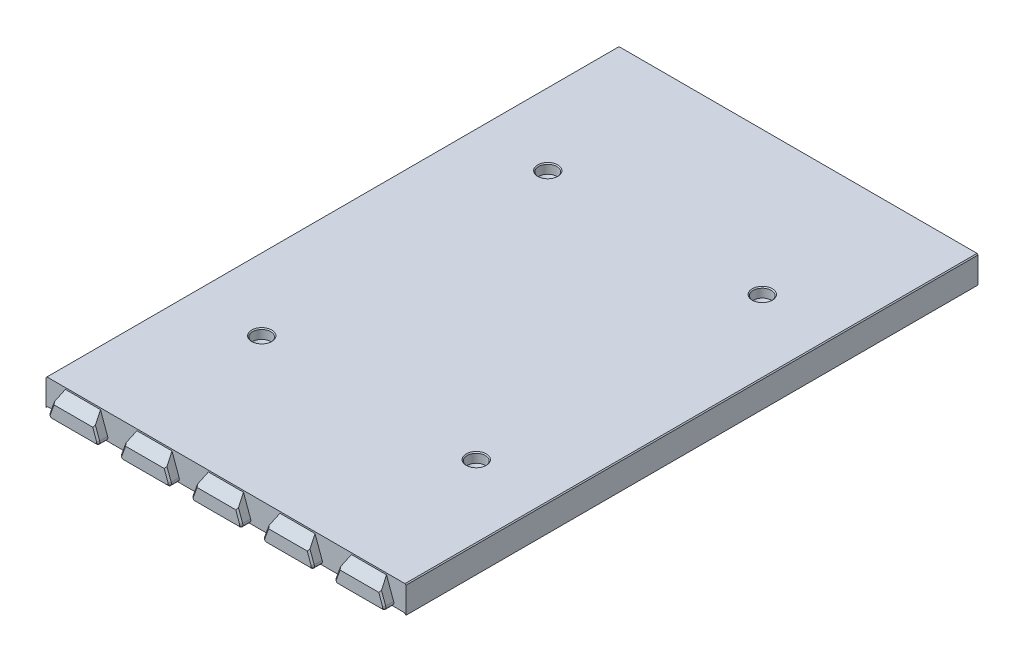
SolidWorks part; units mm, degrees
ref_plane "Front Plane" through (0, 0, 0) normal (0, 0, 1) x (1, 0, 0)
ref_plane "Top Plane" through (0, 0, 0) normal (0, 1, 0) x (1, 0, 0)
ref_plane "Right Plane" through (0, 0, 0) normal (1, 0, 0) x (0, 0, -1)
sketch "Sketch1" plane through (0, 0, 0) normal (0, 0, 1) x (1, 0, 0)
  line L0 (0, 0) -> (0, 8) construction
  line L1 (-56.625, 0) -> (0, 0) construction
  line L2 (-56.625, 0) -> (-56.625, 8)
  line L3 (-56.625, 8) -> (56.625, 8)
  line L5 (-56.625, 0) -> (-54.625, 0)
  line L6 (-54.625, 0) -> (-54.625, 6)
  line L7 (-54.625, 6) -> (54.625, 6)
  line L9 (54.625, 0) -> (54.625, 6)
  line L10 (56.625, 0) -> (54.625, 0)
  line L11 (56.625, 0) -> (56.625, 8)
  point P8 (0, 6)
  dimension "D2" = 6
  dimension "D1" = 56.625
  dimension "D3" = 2
  dimension "D4" = 2
extrude "Boss-Extrude1" add sketch "Sketch1" against normal blind 90
sketch "Sketch7" plane through (0, 0, 0) normal (0, 0, 1) x (1, 0, 0)
  line L2 (-54.625, 0) -> (54.625, 0)
  line L13 (-54.625, 0) -> (-54.625, 6)
  line L15 (-54.625, 6) -> (54.625, 6)
  line L16 (54.625, 0) -> (54.625, 6)
  line M3 (-54.625, 0) -> (-54.625, 6)
  line M4 (-54.625, 6) -> (54.625, 6)
  line M5 (54.625, 6) -> (54.625, 0)
extrude "Boss-Extrude7" add sketch "Sketch7" against normal blind 1 contours M4 M3 | M5 region at (0, 3, 0)
sketch "Sketch2" plane through (0, 0, 0) normal (0, 0, 1) x (1, 0, 0)
  line L14 (39.6618, 8) -> (36.75, 0)
  line L15 (56.625, 8) -> (-56.625, 8) construction
  line L16 (-56.625, 0) -> (56.625, 0) construction
  line L17 (36.75, 0) -> (53.25, 0)
  line L18 (39.6618, 8) -> (50.3382, 8)
  line L19 (-56.625, 0) -> (56.625, 0) construction
  line L21 (50.3382, 8) -> (53.25, 0)
  line L24 (33.75, 0) -> (33.75, 8) construction
  line L27 (17.1618, 8) -> (14.25, 0)
  line L28 (17.1618, 8) -> (27.8382, 8)
  line L29 (14.25, 0) -> (30.75, 0)
  line L30 (27.8382, 8) -> (30.75, 0)
  line L31 (-5.3382, 8) -> (-8.25, 0)
  line L32 (-5.3382, 8) -> (5.3382, 8)
  line L33 (-8.25, 0) -> (8.25, 0)
  line L34 (5.3382, 8) -> (8.25, 0)
  line L35 (-27.8382, 8) -> (-30.75, 0)
  line L36 (-27.8382, 8) -> (-17.1618, 8)
  line L37 (-30.75, 0) -> (-14.25, 0)
  line L38 (-17.1618, 8) -> (-14.25, 0)
  line L39 (39.6618, 8) -> (17.1618, 8) construction
  line L40 (56.25, 8) -> (56.25, 0) construction
  line L41 (56.625, 0) -> (56.625, 8) construction
  line L42 (-56.25, 8) -> (-56.25, 0) construction
  line L43 (-56.625, 8) -> (-56.625, 0) construction
  line L44 (-50.3382, 8) -> (-53.25, 0)
  line L45 (-50.3382, 8) -> (-39.6618, 8)
  line L46 (-53.25, 0) -> (-36.75, 0)
  line L47 (-39.6618, 8) -> (-36.75, 0)
  point P22 (45, 8)
  point P23 (22.5, 8)
  dimension "D1" = 70
  dimension "D2" = 0.375
  dimension "D3" = 3
  dimension "D4" = 3
  dimension "D5" = 70
  dimension "D7" = 22.5
  dimension "D8" = 22.5
  dimension "D9" = 0.375
  dimension "D10" = 25.5
  dimension "D11" = 8
  dimension "D6" = 5
extrude "Boss-Extrude4" add sketch "Sketch2" along normal blind 3
sketch "Sketch8" plane through (0, 0, 0) normal (0, -1, 0) x (1, 0, 0)
  line L0 (-56.625, -22.5) -> (56.625, -22.5) construction
  line L1 (-55.1, -24.7417) -> (-51.4, -23.395)
  line L2 (56.625, -90) -> (56.625, 0) construction
  line L3 (-56.625, 0) -> (-53.25, 0) construction
  line L4 (-55.25, -24.9559) -> (-55.25, -20.0441) construction
  line L5 (-55.25, -20.0441) -> (-51.25, -21.5) construction
  line L6 (-51.25, -21.5) -> (-51.25, -23.5) construction
  line L7 (-55.25, -90) -> (-55.25, -87.5441) construction
  line L8 (-55.25, -87.5441) -> (-51.25, -89) construction
  line L9 (-51.25, -89) -> (-51.25, -90) construction
  line L10 (-54.625, -90) -> (54.625, -90) construction
  line L11 (-51.25, -90) -> (-55.25, -90) construction
  line L12 (-55.25, -24.9559) -> (-51.25, -23.5) construction
  line L13 (0, -90) -> (0, 0) construction
  line L22 (-51.4, -21.605) -> (-51.4, -23.395)
  line L23 (-56.625, -90) -> (-56.625, 0) construction
  line L28 (-56.625, -90) -> (-54.625, -90) construction
  line L33 (-55.1, -20.2583) -> (-51.4, -21.605)
  line L34 (-55.1, -24.7417) -> (-55.1, -20.2583)
  line L35 (-55.1, -87.7583) -> (-51.4, -89.105)
  line L36 (-51.4, -89.105) -> (-51.4, -89.85)
  line L37 (-51.4, -89.85) -> (-55.1, -89.85) construction
  line L38 (-55.1, -89.85) -> (-55.1, -87.7583)
  line L39 (-55.1, -89.85) -> (-55.1, -90)
  line L40 (-55.1, -90) -> (-51.4, -90)
  line L41 (-51.4, -90) -> (-51.4, -89.85)
  line L42 (55.1, -90) -> (51.4, -90)
  line L43 (55.1, -89.85) -> (55.1, -90)
  line L44 (55.1, -89.85) -> (55.1, -87.7583)
  line L45 (55.1, -87.7583) -> (51.4, -89.105)
  line L46 (51.4, -89.105) -> (51.4, -89.85)
  line L47 (51.4, -90) -> (51.4, -89.85)
  line L48 (55.1, -24.7417) -> (55.1, -20.2583)
  line L49 (55.1, -20.2583) -> (51.4, -21.605)
  line L50 (51.4, -21.605) -> (51.4, -23.395)
  line L51 (55.1, -24.7417) -> (51.4, -23.395)
  point P19 (-51.25, -22.5)
  dimension "D1" = 22.5
  dimension "D2" = 0.15
  dimension "D3" = 70
  dimension "D4" = 4
  dimension "D5" = 1.375
  dimension "D6" = 4
  dimension "D7" = 70
  dimension "D8" = 1
  dimension "D9" = 1
extrude "Boss-Extrude8" add sketch "Sketch8" against normal up to next and the other way blind 2
chamfer "Chamfer4" distance 0.5 angle 45 14 edges at (53.25, -2, -20.9317) (55.1, -2, -22.5) (53.25, -2, -24.0683) (51.4, -2, -22.5) (-53.25, -2, -20.9317) (-51.4, -2, -22.5) (-53.25, -2, -24.0683) (-55.1, -2, -22.5) (-51.4, -2, -89.5525) (-55.1, -2, -88.8792) (-53.25, -2, -88.4317) (51.4, -2, -89.5525) (55.1, -2, -88.8792) (53.25, -2, -88.4317)
fillet "Fillet4" radius 1 10 edges at (53.25, 0, 1.5) (36.75, 0, 1.5) (30.75, 0, 1.5) (14.25, 0, 1.5) (8.25, 0, 1.5) (-8.25, 0, 1.5) (-14.25, 0, 1.5) (-30.75, 0, 1.5) (-36.75, 0, 1.5) (-53.25, 0, 1.5)
chamfer "Chamfer6" distance 0.5 angle 45 25 edges at (38.4501, 4.671, 3) (51.5499, 4.671, 3) (45, 0, 3) (-29.0499, 4.671, 3) (-22.5, 0, 3) (-15.9501, 4.671, 3) (-6.5499, 4.671, 3) (0, 0, 3) (6.5499, 4.671, 3) (15.9501, 4.671, 3) (29.0499, 4.671, 3) (22.5, 0, 3) (-51.5499, 4.671, 3) (-45, 0, 3) (-38.4501, 4.671, 3) (-52.641, 0.4264, 3) (-37.359, 0.4264, 3) (-30.141, 0.4264, 3) (-14.859, 0.4264, 3) (-7.641, 0.4264, 3) (7.641, 0.4264, 3) (14.859, 0.4264, 3) (30.141, 0.4264, 3) (37.359, 0.4264, 3) (52.641, 0.4264, 3)
fillet "Fillet2" radius 2 19 edges at (0, 6, -1) (-54.625, 3, -1) (54.625, 6, -10.7156) (54.625, 3, -1) (-54.625, 6, -10.7156) (53.0125, 6, -21.0181) (54.625, 3, -24.5688) (51.4, 6, -22.5) (53.0125, 6, -23.9819) (51.4, 6, -89.5525) (54.625, 3, -87.9312) (54.625, 6, -56.25) (53.0125, 6, -88.5181) (-51.4, 6, -89.5525) (-53.0125, 6, -88.5181) (-51.4, 6, -22.5) (-53.0125, 6, -21.0181) (-53.0125, 6, -23.9819) (-54.625, 6, -56.25)
mirror "Mirror2" about plane through (0, 0, -90) normal (0, 0, 1) of "Fillet4", "Boss-Extrude1", "Boss-Extrude7", "Boss-Extrude4", "Boss-Extrude8", "Chamfer4", "Fillet2", "Chamfer6"
sketch "Sketch9" plane through (0, 0, 0) normal (0, 1, 0) x (1, 0, 0)
  line L16 (0, 90) -> (0, 0) construction
  line L17 (-56.625, 90) -> (56.625, 90) construction
  line L20 (56.625, 180) -> (56.625, 0) construction
  line L21 (-56.625, 180) -> (-56.625, 0) construction
  circle A0 centre (-33.75, 45) radius 5
  circle A4 centre (33.75, 45) radius 5
  circle A5 centre (33.75, 135) radius 5
  circle A6 centre (-33.75, 135) radius 5
  point P23 (0, 90)
  point P24 (0, 90)
  dimension "D3" = 10
  dimension "D1" = 33.75
  dimension "D2" = 45
extrude "Boss-Extrude9" add sketch "Sketch9" along normal up to next
fillet "Fillet3" radius 3 4 edges at (-33.75, 6, -50) (33.75, 6, -50) (-33.75, 6, -140) (33.75, 6, -140)
sketch "Sketch10" plane through (0, 0, 0) normal (0, 1, 0) x (1, 0, 0)
  circle A0 centre (-33.75, 135) radius 1.85
  circle A1 centre (-33.75, 45) radius 1.85
  circle A2 centre (33.75, 45) radius 1.85
  circle A3 centre (33.75, 135) radius 1.85
  dimension "D1" = 3.7
extrude "Cut-Extrude2" cut sketch "Sketch10" along normal through all
sketch "Sketch11" plane through (0, 8, 0) normal (0, 1, 0) x (1, 0, 0)
  circle A0 centre (-33.75, 135) radius 2.85
  circle A1 centre (33.75, 135) radius 2.85
  circle A2 centre (33.75, 45) radius 2.85
  circle A3 centre (-33.75, 45) radius 2.85
  dimension "D1" = 5.7
extrude "Cut-Extrude3" cut sketch "Sketch11" against normal blind 3
chamfer "Chamfer7" distance 1 angle 45 4 edges at (33.75, 5, -133.15) (-33.75, 5, -133.15) (33.75, 5, -43.15) (-33.75, 5, -43.15)
sketch "Sketch12" plane through (0, 0, 0) normal (1, 0, 0) x (0, 0, -1)
  line L0 (0, 7.5) -> (-3, 4.5)
  line L1 (-3, 1.171) -> (-3, 8) construction
  line L2 (-3, 4.5) -> (-3, 7.5)
  line L3 (-3, 7.5) -> (0, 7.5) construction
  line L4 (90, 8) -> (90, 0) construction
  line L5 (180, 8) -> (0, 8) construction
  line L6 (180, 0) -> (0, 0) construction
  line L8 (183, 4.5) -> (183, 7.5)
  line L9 (180, 7.5) -> (183, 4.5)
  line L10 (0, 0) -> (0, 8) construction
  line L11 (-3, 8) -> (-2.5, 8) construction
  line L12 (-3, 7.5) -> (-3, 8)
  line L13 (-3, 8) -> (0, 8)
  line L14 (0, 8) -> (0, 7.5)
  line L15 (183, 7.5) -> (180, 7.5) construction
  line L16 (180, 8) -> (180, 7.5)
  line L17 (183, 8) -> (180, 8)
  line L18 (183, 7.5) -> (183, 8)
  dimension "D1" = 45
  dimension "D2" = 3
  dimension "D3" = 0.5
extrude "Cut-Extrude4" cut sketch "Sketch12" against normal through all both and the other way through all
sketch "Sketch13" plane through (0, 0, -180) normal (0, 0, -1) x (-1, 0, 0)
  line L0 (-56.125, 0) -> (-56.625, -0.5)
  line L1 (-51.8219, 0) -> (-56.625, 0) construction
  line L2 (-56.625, -0.5) -> (-56.625, 0)
  line L3 (-56.625, 0) -> (-56.125, 0)
  line L4 (0, 0) -> (0, 8) construction
  line L5 (-56.625, 8) -> (56.625, 8) construction
  line L6 (56.625, 0) -> (56.125, 0)
  line L7 (56.625, -0.5) -> (56.625, 0)
  line L8 (56.125, 0) -> (56.625, -0.5)
  dimension "D1" = 0.5
  dimension "D2" = 0.5
extrude "Boss-Extrude10" add sketch "Sketch13" against normal up to surface (180 mm away) up to face at (0, 2.9992, 0)
chamfer "Chamfer8" distance 0.3 angle 45 6 edges at (-56.625, 8, -90) (56.625, 8, -90) (-33.75, 8, -42.15) (33.75, 8, -42.15) (33.75, 8, -132.15) (-33.75, 8, -132.15)
